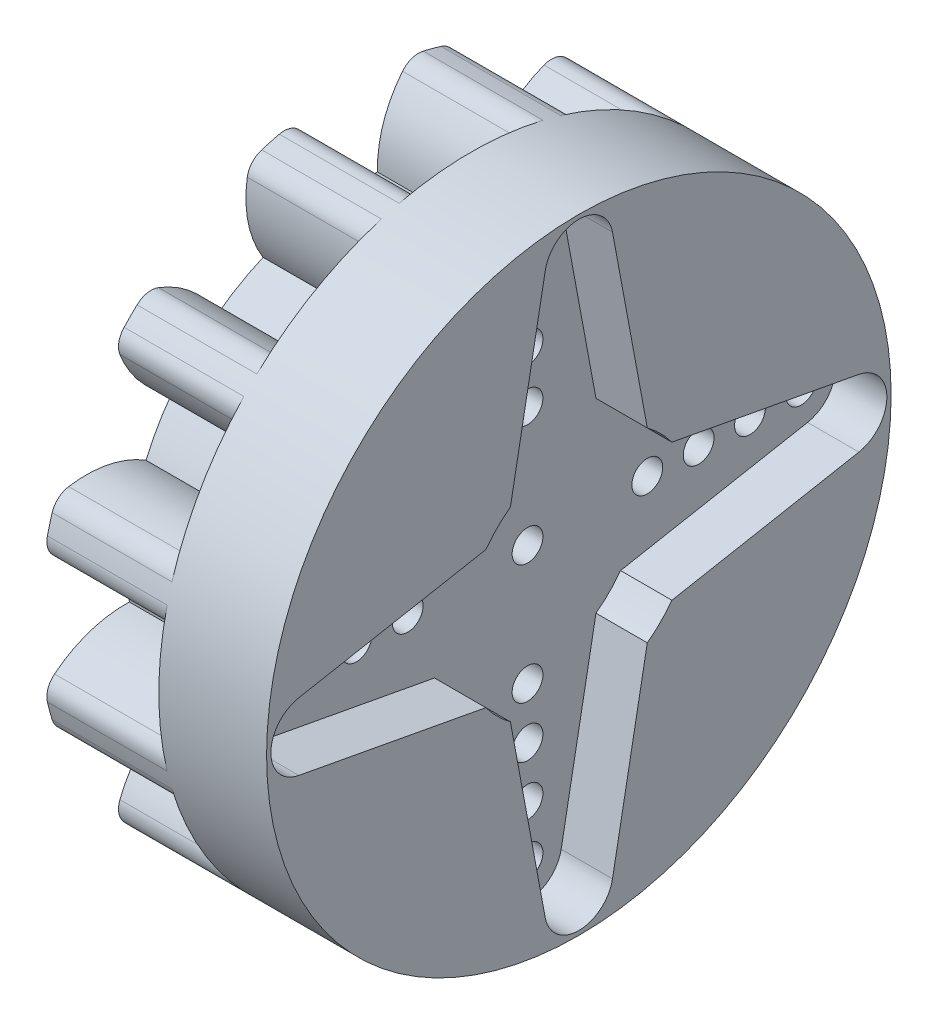
SolidWorks part; units mm, degrees
ref_plane "Plane1" through (0, 0, 0) normal (0, 0, 1) x (1, 0, 0)
ref_plane "Plane2" through (0, 0, 0) normal (0, 1, 0) x (1, 0, 0)
ref_plane "Plane3" through (0, 0, 0) normal (1, 0, 0) x (0, 0, -1)
sketch "HoldingSke" plane through (0, 0, 0) normal (0, 1, 0) x (1, 0, 0)
  line L0 (0, 0) -> (0.3557, -0.0756)
  line L1 (-15, 0) -> (100, 0) construction
  line L2 (0, 0) -> (-2.1039, 2.3779)
  line L3 (0, 0) -> (-11.863, 4.5341)
  line L4 (0, 0) -> (8.4473, 1.7955)
  line L5 (0, 0) -> (-46.8476, -17.4728)
  line L6 (0, 0) -> (-5.8027, -3.9151)
  line L7 (-2.1039, 2.3779) -> (8.6586, 51.2059)
  line L8 (-76.2, 54.61) -> (-76.1, 54.61)
  line L9 (-71.009, 38.7566) -> (-53.1078, 45.2721)
  line L10 (-76.2, 71.12) -> (104.1128, 71.12)
  line L11 (0, 0) -> (-7, 0)
  line L12 (-76.2, 101.6) -> (-76.103, 101.6)
  line L13 (24.9733, 27.94) -> (52.9518, 28.4284)
  line L14 (24.9733, 27.94) -> (24.9743, 27.94)
  line L15 (24.9733, 27.94) -> (100.4006, 29.5858)
  line L16 (-63.627, -2.75) -> (-12.827, -2.75)
  circle A0 centre (0, 0) radius 0.4
  circle A1 centre (0, 0) radius 13.0615
  circle A2 centre (0, 0) radius 37.5
  circle A3 centre (0, 0) radius 0.4
  dimension "Num_teeth" = 12
  dimension "Pitch_radius" = 180.3128
  dimension "Width" = 7
  dimension "Thickness" = 7
sketch "BasProSke" plane through (0, 0, 0) normal (0, 1, 0) x (1, 0, 0)
  line L0 (-10, 0) -> (60, 0) construction
  line L1 (0, 0) -> (0, 19.25)
  line L2 (0, 0) -> (7, 0)
  line L3 (7, 0) -> (7, 19.25)
  line L4 (7, 19.25) -> (0, 19.25)
  dimension "Thickness" = 7
  dimension "Diameter" = 38.5
revolve "Base-Revolve" add sketch "BasProSke" angle 360 about L0
sketch "TooCutSke" plane through (0, 0, 0) normal (1, 0, 0) x (0, 0, -1)
  line L1 (0, 0) -> (0, 107) construction
  line L2 (0, 0) -> (-2.3232, 16.3356) construction
  line L3 (0, 0) -> (-8.4791, 31.6443) construction
  line L4 (-2.3232, 16.3356) -> (-4.2395, 15.8221) construction
  arc A0 (1.5356, 12.9709) -> (-1.5356, 12.9709) centre (0, 0) ccw
  arc A1 (4.5337, 18.7346) -> (-4.5337, 18.7346) centre (0, 0) ccw
  circle A2 centre (0, 0) radius 16.5 construction
  circle A3 centre (0, 0) radius 15.5049 construction
  arc A4 (-1.5356, 12.9709) -> (-4.5337, 18.7346) centre (-8.1316, 13.2015) ccw
  arc A5 (4.5337, 18.7346) -> (1.5356, 12.9709) centre (8.1316, 13.2015) ccw
extrude "ToothCut" cut sketch "TooCutSke" along normal through all
fillet "Breaks" [suppressed] radius 0.055 tangent propagation no
fillet "RootFillets" [suppressed] radius 0.6885
pattern_circular "TeethCuts" count 12 every 30 about axis through (-10, 0, 0) along (1, 0, 0) of "ToothCut", "RootFillets", "Breaks"
sketch "HubNeaOneSke" plane through (0, 0, 0) normal (-1, 0, 0) x (0, 0, 1)
  circle A0 centre (0, 0) radius 13.0615
  dimension "Diameter" = 26.123
extrude "HubNearOne" [suppressed] add sketch "HubNeaOneSke" along normal blind 43.0001
sketch "HubNeaBotSke" plane through (0, 0, 0) normal (-1, 0, 0) x (0, 0, 1)
  circle A0 centre (0, 0) radius 13.0615
  dimension "Diameter" = 26.123
extrude "HubNearBoth" [suppressed] add sketch "HubNeaBotSke" along normal blind 21.5
ref_plane "FarPln" through (7, 0, 0) normal (1, 0, 0) x (0, 0, -1)
sketch "HubFarSke" plane through (7, 0, 0) normal (1, 0, 0) x (0, 0, -1)
  circle A0 centre (0, 0) radius 13.0615
  dimension "Diameter" = 26.123
extrude "HubFar" [suppressed] add sketch "HubFarSke" along normal blind 21.5
sketch "BorSke" plane through (0, 0, 0) normal (1, 0, 0) x (0, 0, -1)
  circle A0 centre (0, 0) radius 0.4
  dimension "Diameter" = 0.8
extrude "Bore" cut sketch "BorSke" along normal mid plane 100.0001
sketch "KeySke" plane through (0, 0, 0) normal (1, 0, 0) x (0, 0, -1)
  line L0 (-0.05, 0) -> (-0.05, 0.5)
  line L1 (-0.05, 0.5) -> (0.05, 0.5)
  line L2 (0.05, 0.5) -> (0.05, 0)
  line L3 (0, 0) -> (0, 34) construction
  line L4 (-0.05, 0) -> (0.05, 0)
  dimension "Width" = 0.1
extrude "Keyway" [suppressed] cut sketch "KeySke" along normal mid plane 100.0001
pattern_circular "Keyway2" [suppressed] count 2 every 90 about axis through (-10, 0, 0) along (1, 0, 0) reverse direction yes
sketch "Эскиз1" plane through (7, 0, 0) normal (1, 0, 0) x (0, 0, -1)
  circle A0 centre (0, 0) radius 18.5
  circle A1 centre (0, 0) radius 0.4 construction
  circle A2 centre (0, 0) radius 0.4
  dimension "D1" = 37
extrude "Бобышка-Вытянуть1" add sketch "Эскиз1" along normal blind 6.3
sketch "Эскиз13" plane through (13.3, 0, 0) normal (1, 0, 0) x (0, 0, -1)
  circle A2 centre (0, 0) radius 0.9
  circle A3 centre (0, 0) radius 18.25
  dimension "D1" = 1.8
  dimension "D2" = 36.5
extrude "Вырез-Вытянуть11" cut sketch "Эскиз13" against normal through all flip side to cut
fillet "Скругление1" radius 1.2 24 edges at (3.5, -5.9182, -17.2638) (3.5, -3.5066, -17.91) (3.5, 3.5066, -17.91) (3.5, 5.9182, -17.2638) (3.5, 11.9918, -13.7572) (3.5, 13.7572, -11.9918) (3.5, 17.2638, -5.9182) (3.5, 17.91, -3.5066) (3.5, 17.2638, 5.9182) (3.5, 17.91, 3.5066) (3.5, 13.7572, 11.9918) (3.5, 11.9918, 13.7572) (3.5, 5.9182, 17.2638) (3.5, 3.5066, 17.91) (3.5, -3.5066, 17.91) (3.5, -5.9182, 17.2638) (3.5, -11.9918, 13.7572) (3.5, -13.7572, 11.9918) (3.5, -17.2638, 5.9182) (3.5, -17.91, 3.5066) (3.5, -17.91, -3.5066) (3.5, -17.2638, -5.9182) (3.5, -11.9918, -13.7572) (3.5, -13.7572, -11.9918)
sketch "Эскиз14" plane through (13.3, 0, 0) normal (1, 0, 0) x (0, 0, -1)
  line L0 (0, 19.4075) -> (0, -20.0118) construction
  line L1 (-20.8718, 0) -> (19.7562, 0) construction
  line L2 (-1.9662, 16.3659) -> (-4, 5.4371)
  line L3 (1.9662, 16.3659) -> (4, 5.4371)
  line L4 (16.3659, 1.9662) -> (5.4371, 4)
  line L5 (16.3659, -1.9662) -> (5.4371, -4)
  line L6 (1.9662, -16.3659) -> (4, -5.4371)
  line L7 (-1.9662, -16.3659) -> (-4, -5.4371)
  line L8 (-16.3659, -1.9662) -> (-5.4371, -4)
  line L9 (-16.3659, 1.9662) -> (-5.4371, 4)
  circle A0 centre (0, 0) radius 0.9 construction
  circle A1 centre (0, 0) radius 0.9
  circle A2 centre (0, 0) radius 6.75
  arc A3 (-1.9662, 16.3659) -> (1.9662, 16.3659) centre (0, 16) cw
  circle A4 centre (0, 16) radius 0.9
  circle A5 centre (0, 13) radius 0.9
  circle A6 centre (0, 10) radius 0.9
  circle A7 centre (0, 7) radius 0.9
  arc A8 (16.3659, 1.9662) -> (16.3659, -1.9662) centre (16, 0) cw
  circle A9 centre (16, 0) radius 0.9
  circle A10 centre (13, 0) radius 0.9
  circle A11 centre (10, 0) radius 0.9
  circle A12 centre (7, 0) radius 0.9
  arc A13 (1.9662, -16.3659) -> (-1.9662, -16.3659) centre (0, -16) cw
  circle A14 centre (0, -16) radius 0.9
  circle A15 centre (0, -13) radius 0.9
  circle A16 centre (0, -10) radius 0.9
  circle A17 centre (0, -7) radius 0.9
  arc A18 (-16.3659, -1.9662) -> (-16.3659, 1.9662) centre (-16, 0) cw
  circle A19 centre (-16, 0) radius 0.9
  circle A20 centre (-13, 0) radius 0.9
  circle A21 centre (-10, 0) radius 0.9
  circle A22 centre (-7, 0) radius 0.9
  point P13 (0, 0)
  point P22 (0, 0)
  point P23 (0, 18)
  point P24 (0, 0)
  point P37 (18, 0)
  point P50 (0, -18)
  point P63 (-18, 0)
  point P64 (0, 0)
  point P65 (0, 0)
  circle M7 centre (0, 0) radius 0.9
  dimension "D1" = 13.5
  dimension "D2" = 7
  dimension "D8" = 1.8
  dimension "D3" = 3
  dimension "D4" = 3
  dimension "D5" = 3
  dimension "D6" = 18
  dimension "D7" = 8
  dimension "D9" = 4
extrude "Вырез-Вытянуть12" cut sketch "Эскиз14" against normal blind 3 contours A22 A2 L9 A18 L8 A21 A20 A19 | A22 A2 A17 A12 A7 M7 | A7 A2 L3 A3 L2 A6 A5 A4 | A12 A2 L5 A8 L4 A11 A10 A9 | A17 A2 L7 A13 L6 A16 A15 A14 region at (13.3, 11.1792, 0) region at (13.3, 6.0924, 2.4339) region at (13.3, 0, 11.1792) region at (13.3, 0, -11.1792) region at (13.3, -11.1792, 0)
extrude "Вырез-Вытянуть13" cut sketch "Эскиз14<3>" against normal blind 5 contours A2 A22 | A2 A22 | A20 | A19 | A21 | A7 | A6 | A5 | A4 | A12 | A11 | A10 | A9 | A17 | A16 | A15 | A14 region at (13.3, 0, 6.4699) region at (13.3, 0, 7.2418) region at (13.3, 0, 13)
sketch "Эскиз14<3>" plane through (13.3, 0, 0) normal (1, 0, 0) x (0, 0, -1) same geometry as "Эскиз14"
equation "' \"Module@HoldingSke\" = 6.35"
equation "' \"Num_teeth@HoldingSke\" = 12"
equation "' \"Ap@HoldingSke\" =  20"
equation "' \"Ap@HoldingSke\" = 20"
equation "' \"Width@HoldingSke\" = 0.5 * 25.4"
equation "' \"Hub_dia@HoldingSke\"= 1 * 25.4"
equation "' \"Hub_dia@HoldingSke\" = 1 * 25.4"
equation "' \"Overall_len@HoldingSke\" = 1.0 * 25.4"
equation "' \"Bore@HoldingSke\" = 0.75 * 25.4"
equation "' \"T_dim@HoldingSke\" = 0.1 * 25.4"
equation "' \"Width@KeySke\" = 0.25 * 25.4"
equation "' \"Show_teeth@HoldingSke\" = 13"
equation "' \"Backlash@HoldingSke\" = 0.009 * 25.4"
equation "' \"Addendum_fac@HoldingSke\" = 1.0"
equation "' \"Dedendum_fac@HoldingSke\" = 1.25"
equation "' \"Dedendum_add@HoldingSke\" = 0.00005 * 25.4"
equation "' \"Clearance_fac@HoldingSke\" = 0.25"
equation "\"Pitch@HoldingSke\" = 1 / \"Module@HoldingSke\""
equation "\"Overcut_dia@TooCutSke\" = (\"Num_teeth@HoldingSke\" + 2 * \"Addendum_fac@HoldingSke\") / \"Pitch@HoldingSke\" + 0.002 * 25.4"
equation "\"Pitch_dia@TooCutSke\" = \"Num_teeth@HoldingSke\" / \"Pitch@HoldingSke\""
equation "\"Base_dia@TooCutSke\" = \"Num_teeth@HoldingSke\" / \"Pitch@HoldingSke\" * cos((\"Ap@HoldingSke\"  * 3.14159265 / 180))"
equation "\"Root_dia@TooCutSke\" = (\"Num_teeth@HoldingSke\" + 2) / \"Pitch@HoldingSke\" - 2 * (\"Addendum_fac@HoldingSke\" + \"Dedendum_fac@HoldingSke\") / \"Pitch@HoldingSke\" - \"Dedendum_add@HoldingSke\" * 2"
equation "\"Half_ang@TooCutSke\" = 180 / \"Num_teeth@HoldingSke\""
equation "\"Half_CT@TooCutSke\" = \"Num_teeth@HoldingSke\" / \"Pitch@HoldingSke\" * sin((3.14159265 / 2 / \"Num_teeth@HoldingSke\")) / 2 - 7 * \"Backlash@HoldingSke\" / 4"
equation "\"Flank_rad@TooCutSke\" = \"Num_teeth@HoldingSke\" / \"Pitch@HoldingSke\" / 5"
equation "\"Radius@RootFillets\" = \"Clearance_fac@HoldingSke\" / \"Pitch@HoldingSke\" + \"Dedendum_add@HoldingSke\""
equation "\"Break_rad@Breaks\" = 0.02 / \"Pitch@HoldingSke\""
equation "\"Thickness@HoldingSke\" = \"Width@HoldingSke\""
equation "\"OAL@HoldingSke\" = \"Thickness@HoldingSke\""
equation "\"MHD@HoldingSke\" = (\"Num_teeth@HoldingSke\" + 2) / \"Pitch@HoldingSke\" - 2 * (\"Addendum_fac@HoldingSke\" + \"Dedendum_fac@HoldingSke\")  / \"Pitch@HoldingSke\" - \"Dedendum_add@HoldingSke\" * 2"
equation "\"MBD@HoldingSke\" = (\"Num_teeth@HoldingSke\" + 2) / \"Pitch@HoldingSke\" - 2 * (\"Addendum_fac@HoldingSke\" + \"Dedendum_fac@HoldingSke\")  / \"Pitch@HoldingSke\" - \"Dedendum_add@HoldingSke\" * 2 - 0.002 * 25.4"
equation "\"MHD@HoldingSke\" = ((sgn( \"MHD@HoldingSke\" - \"Hub_dia@HoldingSke\" )-1)*( \"MHD@HoldingSke\" - \"Hub_dia@HoldingSke\" ))/-2+ \"Hub_dia@HoldingSke\""
equation "\"MBD@HoldingSke\" = ((sgn( \"MBD@HoldingSke\" - \"Bore@HoldingSke\" )-1)*( \"MBD@HoldingSke\" - \"Bore@HoldingSke\" ))/-2+ \"Bore@HoldingSke\""
equation "\"OAL@HoldingSke\" = ((sgn( \"OAL@HoldingSke\" - \"Overall_len@HoldingSke\" )+1)*( \"OAL@HoldingSke\" - \"Overall_len@HoldingSke\" ))/2 + \"Overall_len@HoldingSke\" + 0.000002 * 25.4"
equation "\"Num_teeth@TeethCuts\" = int( \"Show_teeth@HoldingSke\" ) + 1"
equation "\"Num_teeth@TeethCuts\" = ((sgn( \"Num_teeth@TeethCuts\" - \"Num_teeth@HoldingSke\" )-1)*( \"Num_teeth@TeethCuts\" - \"Num_teeth@HoldingSke\" ))/-2+ \"Num_teeth@HoldingSke\""
equation "\"Num_teeth@TeethCuts\" = ((sgn( \"Num_teeth@TeethCuts\" - 2.0)+1)*( \"Num_teeth@TeethCuts\" - 2.0))/2 +2.0"
equation "\"Angle@TeethCuts\" = 360.0 / \"Num_teeth@HoldingSke\""
equation "\"Diameter@BasProSke\" = (\"Num_teeth@HoldingSke\" + 2 * \"Addendum_fac@HoldingSke\") / \"Pitch@HoldingSke\""
equation "\"Thickness@BasProSke\"  = \"Thickness@HoldingSke\""
equation "' \"Fillet_rad@BasProSke\" =  \"Thickness@HoldingSke\" * 0.05"
equation "' \"Fillet_rad@BasProSke\" = \"Thickness@HoldingSke\" * 0.05"
equation "\"MHD@HoldingSke\" = ((sgn( \"MHD@HoldingSke\" - \"Root_dia@TooCutSke\" )-1)*( \"MHD@HoldingSke\" - \"Root_dia@TooCutSke\" ))/-2+ \"Root_dia@TooCutSke\""
equation "\"Diameter@HubNeaOneSke\" = \"MHD@HoldingSke\""
equation "\"Length@HubNearOne\" = \"OAL@HoldingSke\" - \"Thickness@BasProSke\""
equation "\"Diameter@HubNeaBotSke\" = \"MHD@HoldingSke\""
equation "\"Length@HubNearBoth\" = ( \"OAL@HoldingSke\" - \"Thickness@BasProSke\" ) / 2.0"
equation "\"Thickness@FarPln\" = \"Thickness@BasProSke\""
equation "\"Diameter@HubFarSke\" = \"MHD@HoldingSke\""
equation "\"Length@HubFar\" = ( \"OAL@HoldingSke\" - \"Thickness@BasProSke\" ) / 2.0"
equation "\"Diameter@BorSke\" = \"MBD@HoldingSke\""
equation "\"D1@Bore\" = \"OAL@HoldingSke\" * 2.0"
equation "\"D1@Keyway\" = \"OAL@HoldingSke\" * 2.0"
equation "\"Offset@KeySke\" = \"T_dim@HoldingSke\" + \"MBD@HoldingSke\" / 2.0"
